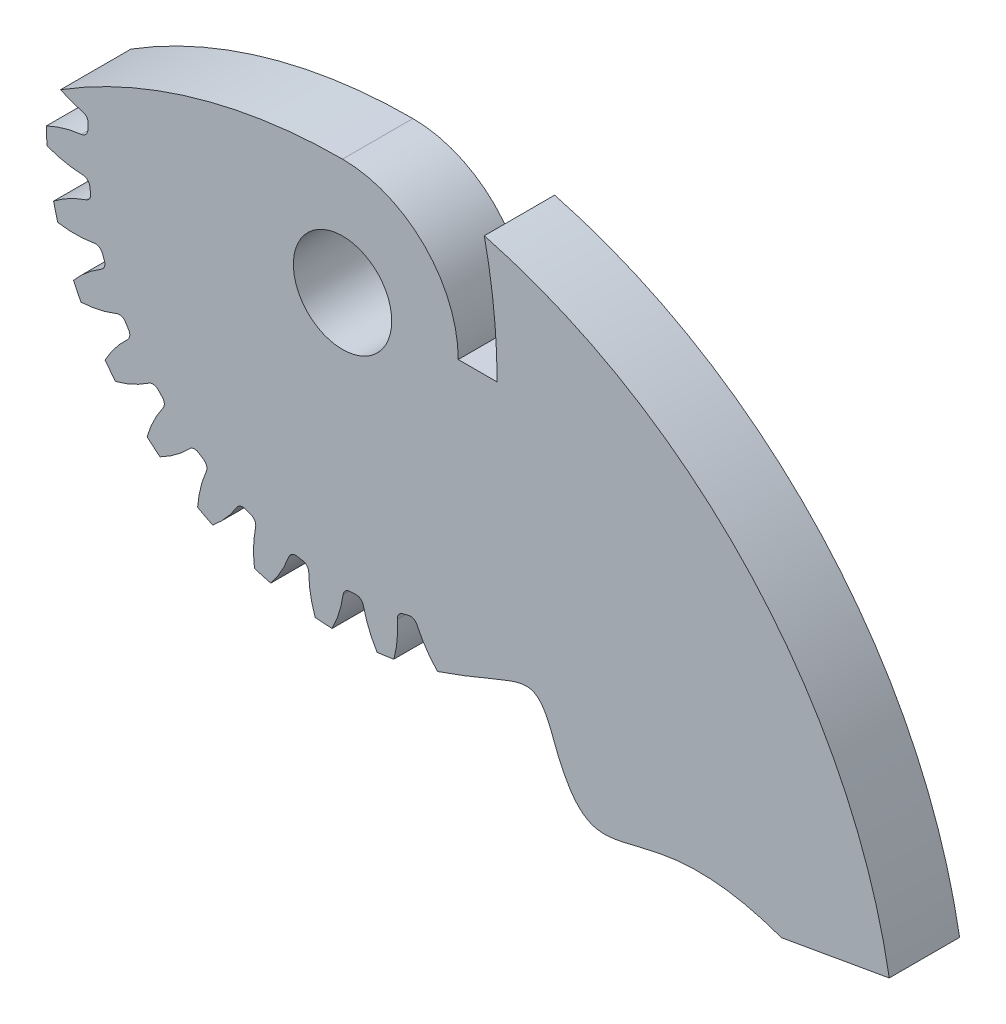
SolidWorks part; units mm, degrees
material "ABS"
ref_plane "Front" through (0, 0, 0) normal (0, 0, 1) x (1, 0, 0)
ref_plane "Top" through (0, 0, 0) normal (0, 1, 0) x (1, 0, 0)
ref_plane "Right" through (0, 0, 0) normal (1, 0, 0) x (0, 0, -1)
sketch "Sketch3" plane through (0, 0, 0) normal (0, 0, 1) x (1, 0, 0)
  circle A0 centre (0, 0) radius 40.64
  dimension "od" = 40.64
extrude "gearBody" add sketch "Sketch3" along normal blind 9.652
sketch "Sketch2" plane through (0, 0, 0) normal (0, 0, 1) x (1, 0, 0)
  line L0 (0, 0) -> (34.0786, 14.1158) construction
  line L1 (45.4751, -11.4855) -> (0, 0) construction
  line L2 (0, 0) -> (36.3143, 0) construction
  line L3 (38.0972, -0.458) -> (37.8451, -4.4001) construction
  line L5 (37.9712, -2.4291) -> (0, 0) construction
  line L7 (0, 0) -> (36.8864, 0) construction
  arc A0 (36.879, -0.7403) -> (36.6727, -3.9649) centre (0, 0) ccw construction
  arc A1 (40.637, 0.4947) -> (40.2427, -5.6687) centre (0, 0) ccw construction
  arc A2 (38.0972, -0.458) -> (37.8451, -4.4001) centre (0, 0) ccw construction
  arc A3 (34.9015, -2.6404) -> (34.9534, -1.8283) centre (0, 0) ccw
  arc A4 (45.4751, -11.4855) -> (35.6466, -3.6712) centre (32.0022, -18.3431) ccw
  arc A5 (45.4751, -11.4855) -> (46.5679, 5.5974) centre (0, 0) ccw
  arc A6 (46.5679, 5.5974) -> (35.8238, -0.9008) centre (34.0786, 14.1158) cw
  arc A7 (34.9534, -1.8283) -> (35.8238, -0.9008) centre (35.9376, -1.8798) cw
  arc A8 (35.6466, -3.6712) -> (34.9015, -2.6404) centre (35.8842, -2.7147) cw
  point P6 (46.5679, 5.5974)
  point P22 (45.4751, -11.4855)
  dimension "baseDia" = 73.7729
  dimension "od" = 81.28
  dimension "pd" = 76.2
  dimension "rd" = 70.0024
  dimension "rFillet" = 0.9855
  dimension "pointX" = 46.5679
  dimension "pointY" = 5.5974
  dimension "CTT" = 3.9421
  dimension "flankCenterAngle" = 22.5
extrude "toothCut" cut sketch "Sketch2" along normal through all
pattern_circular "CirPattern1" count 30 over 360 about axis through (0, 0, 9.652) along (0, 0, -1) of "toothCut"
sketch "hub1Dia" plane through (0, 0, 0) normal (0, 0, -1) x (-1, 0, 0)
  circle A0 centre (0, 0) radius 12.7
  dimension "hub1Dia" = 25.4
sketch "hub2Dia" plane through (0, 0, 9.652) normal (0, 0, 1) x (1, 0, 0)
  circle A0 centre (0, 0) radius 12.7
  dimension "hub2dia" = 25.4
sketch "boreDia" plane through (0, 0, 0) normal (0, 0, 1) x (1, 0, 0)
  circle A0 centre (0, 0) radius 6.7469
  dimension "boreDia" = 13.4937
extrude "bore" cut sketch "boreDia" against normal mid plane 25400
sketch "Sketch4" plane through (0, 0, 9.652) normal (0, 0, 1) x (1, 0, 0)
  circle A0 centre (0, -57.15) radius 76.1746
  arc A2 (-41.7195, 6.5842) -> (41.7195, 6.5842) centre (0, 0) cw
  dimension "D1" = 152.3492
  dimension "D2" = 57.15
extrude "Cut-Extrude1" cut sketch "Sketch4" against normal through all contours A0 region at (0, 26.0638, 9.652)
sketch "Sketch5" plane through (0, 0, 9.652) normal (0, 0, 1) x (1, 0, 0)
  line L0 (0, 19.0246) -> (21.5163, 3.7176)
  line L1 (21.5163, 3.7176) -> (8.9608, -26.928)
  line L2 (8.9608, -26.928) -> (13.028, -38.4952)
  line L3 (0, 0) -> (0, -57.15) construction
  line L4 (0, -57.15) -> (-54.1615, -3.586) construction
  line L5 (0, -57.15) -> (65.9691, -95.2373) construction
  line L9 (0, -57.15) -> (75.0173, -43.9224) construction
  line L12 (60.232, -46.5295) -> (75.0173, -43.9224)
  line L13 (0, -57.15) -> (29.696, -40.005) construction
  line L14 (29.696, -40.005) -> (26.521, -34.5057) construction
  circle A1 centre (0, -57.15) radius 76.1746 construction
  arc A5 (0, 19.0246) -> (75.0173, -43.9224) centre (0, -57.15) cw
  circle A6 centre (0, -57.15) radius 21.59 construction
  circle A12 centre (49.4934, -85.725) radius 40.64 construction
  spline S0 degree 3 poles (13.028, -38.4952) (20.557, -35.948) (26.6517, -31.726) (34.6651, -56.7545) (39.5345, -39.0169) (60.232, -46.5295) knots 0 0 0 0 0.118515 0.218515 1 1 1 1
  point P28 (21.569, -56.1981)
  dimension "D1" = 43.18
  dimension "D3" = 81.28
  dimension "D6" = 152.3492
  dimension "D2" = 120
  dimension "D4" = 57.15
  dimension "D8" = 57.15
  dimension "D7" = 60
  dimension "D9" = 34.29
  dimension "D10" = 6.35
  dimension "D5" = 80
extrude "Boss-Extrude1" add sketch "Sketch5" against normal up to surface (9.652 mm away) up to face at (6.7469, 0, 0)
sketch "Sketch6" plane through (0, 0, 9.652) normal (0, 0, 1) x (1, 0, 0)
  line L1 (-41.2993, 3.0747) -> (-42.3397, 6.1739)
  line L2 (15.875, 0) -> (21.209, 0)
  circle A0 centre (0, -57.15) radius 76.1746 construction
  arc A1 (75.0173, -43.9224) -> (-34.0662, 10.9827) centre (0, -57.15) ccw construction
  circle A2 centre (0, 0) radius 15.875 construction
  arc A3 (0, 15.875) -> (15.875, 0) centre (0, 0) cw
  arc A4 (19.4523, 16.499) -> (-42.3397, 6.1739) centre (0, -57.15) ccw
  arc A5 (0, 15.875) -> (-41.2993, 3.0747) centre (0, -57.15) ccw
  circle A6 centre (0, 0) radius 21.209 construction
  circle A8 centre (-57.15, 0) radius 78.359 construction
  arc A9 (21.209, 0) -> (19.4523, 16.499) centre (-57.15, 0) ccw
  dimension "D4" = 57.15
  dimension "D1" = 31.75
  dimension "D2" = 42.418
  dimension "D3" = 156.718
extrude "Cut-Extrude2" cut sketch "Sketch6" against normal through all
equation "\"Bodytube_OD\"= 6.17in"
equation "\"Bodytube_ID\"= 5.998in"
equation "\"Fwd_Tube_Length\"= 40in"
equation "\"Mid_Tube_Length\"= 1in"
equation "\"Aft_Section_Length\"= 39in"
equation "\"Mid_Coupler_Length\"= 13in"
equation "\"Aft_Lower_Length\"= 22in"
equation "\"AB_Coupler_OD_Length\"= 1in"
equation "\"AB_Coupling_Section_Length\"= 0.375in"
equation "\"AB_Coupler_Length\"= \"AB_Coupler_OD_Length\" + \"AB_Coupling_Section_Length\" * 2"
equation "\"Cutout_Angle\"= 80"
equation "\"AB_Paddle_Height\"= 0.375in"
equation "\"AB_Coupler_Num_Screws\"= 4"
equation "\"Num_Cutouts\"= 3"
equation "\"AB_Coupler_OD\"= 6.17in"
equation "\"AB_Coupler_ID\"= 5.75in"
equation "\"AB_Coupler_Surface_Diameter\"= 5.998in"
equation "\"AB_Coupling_Screw_Diameter\"= 0.15748in"
equation "\"AB_Central_Bushing_Length\"= .4724in"
equation "\"Lead_Screw_Dist\"= 3.4in"
equation "\"Lead_Screw_Diam\"= 0.386in"
equation "\"Lead_Screw_Length\"= (\"Mid_Coupler_Length\" + 2*0.375in + 2*0.5in)"
equation "\"Paddle_Pin_Offset\"= .25in"
equation "\"Paddle_Pin_Radius\"= 2.25in"
equation "\"Fwd_BKHD_From_Top\"= 18in"
equation "\"D1@Sketch4\"=\"Bodytube_ID\""
equation "\"D2@Sketch4\"=\"Paddle_Pin_Radius\""
equation "\"D3@Sketch5\"=\"Paddle_Gear_OD\""
equation "\"D4@Sketch5\"=\"Paddle_Pin_Radius\""
equation "\"Motor_OD\"= 4in"
equation "\"Aft_Upper_Length\"= \"Aft_Section_Length\" - \"Aft_Lower_Length\" - \"AB_Coupler_OD_Length\""
equation "\"Paddle_Gear_OD\"= 3.2in"
equation "\"D5@Sketch5\"=\"Cutout_Angle\""
equation "\"D6@Sketch5\"=\"Bodytube_ID\""
equation "\"D1@Sketch6\"=\"AB_Coupler_ID\"-2*\"Paddle_Pin_Radius\""
equation "\"D2@Sketch6\"=\"Bodytube_OD\"-2*\"Paddle_Pin_Radius\""
equation "\"D3@Sketch6\"=\"Bodytube_OD\""
equation "\"D4@Sketch6\"=\"Paddle_Pin_Radius\""
equation "\"D8@Sketch5\"=\"Paddle_Pin_Radius\""
equation "\"Drive_Gear_OD\"= 1.7in"
equation "\"Fin_Thickness\"= .118in"
equation "\"Guiderail_Cutout_Diameter\"= 1.5in"
equation "\"DB9_Hole_Dist\"= 25mm"
equation "\"D1@Sketch5\"=\"Drive_Gear_OD\""
